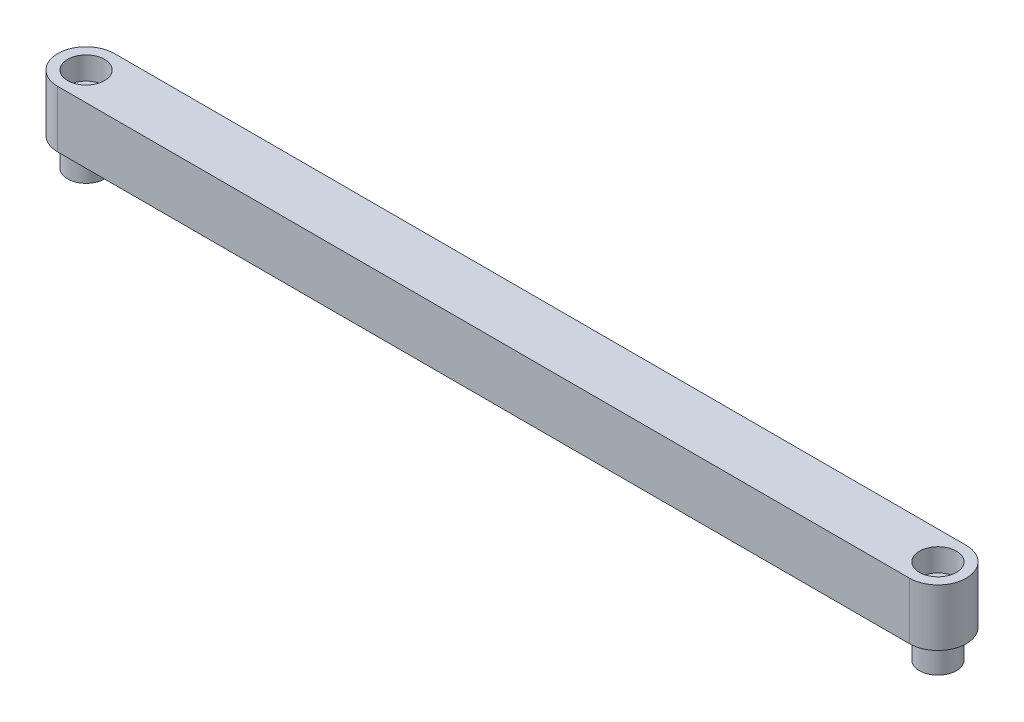
SolidWorks part; units mm, degrees
ref_plane "Front Plane" through (0, 0, 0) normal (0, 0, 1) x (1, 0, 0)
ref_plane "Top Plane" through (0, 0, 0) normal (0, 1, 0) x (1, 0, 0)
ref_plane "Right Plane" through (0, 0, 0) normal (1, 0, 0) x (0, 0, -1)
sketch "Sketch1" plane through (0, 0, 0) normal (0, 1, 0) x (1, 0, 0)
  line L0 (-225, 0) -> (225, 0) construction
  line L1 (-225, 15) -> (225, 15)
  line L2 (-225, -15) -> (225, -15)
  arc A0 (-225, 15) -> (-225, -15) centre (-225, 0) ccw
  arc A1 (225, -15) -> (225, 15) centre (225, 0) ccw
  point P2 (0, 0)
  dimension "D2" = 15
  dimension "D1" = 450
extrude "Boss-Extrude1" add sketch "Sketch1" along normal mid plane 30
sketch "Sketch2" plane through (0, 0, 0) normal (0, 1, 0) x (1, 0, 0)
  circle A0 centre (-225, 0) radius 9.75
  circle A1 centre (225, 0) radius 9.75
  dimension "D1" = 19.5
  dimension "D2" = 19.5
extrude "Cut-Extrude2" cut sketch "Sketch2" along normal through all
extrude "Boss-Extrude2" add sketch "Sketch2<3>" against normal blind 30
sketch "Sketch2<3>" plane through (0, 0, 0) normal (0, 1, 0) x (1, 0, 0) same geometry as "Sketch2"
extrude "Boss-Extrude3" add sketch "Sketch2<4>" along normal blind 3
sketch "Sketch2<4>" plane through (0, 0, 0) normal (0, 1, 0) x (1, 0, 0) same geometry as "Sketch2"
